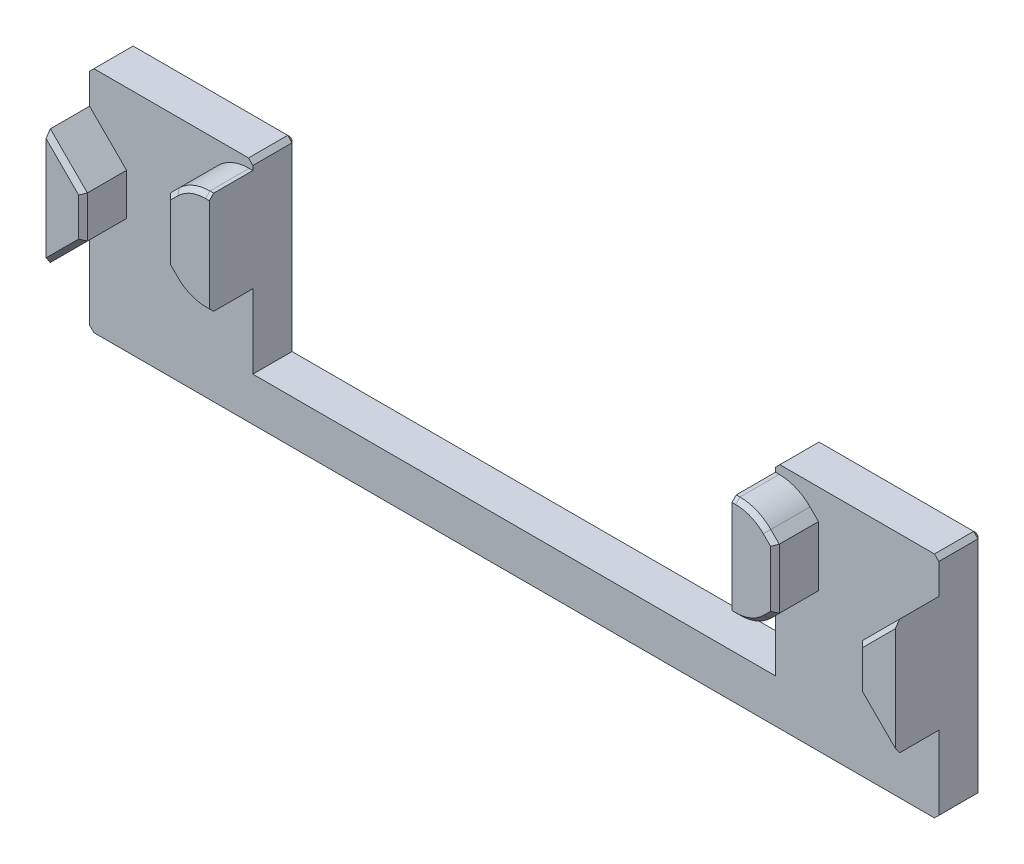
SolidWorks part; units mm, degrees
ref_plane "Front" through (0, 0, 0) normal (0, 0, 1) x (1, 0, 0)
ref_plane "Top" through (0, 0, 0) normal (0, 1, 0) x (1, 0, 0)
ref_plane "Right" through (0, 0, 0) normal (1, 0, 0) x (0, 0, -1)
sketch "Sketch1" plane through (0, 0, 0) normal (0, 0, 1) x (1, 0, 0)
  line L0 (-19.3, -5.25) -> (19.3, -5.25)
  line L5 (19.5, -5.05) -> (19.5, 5.05)
  line L6 (19.3, 5.25) -> (12.2, 5.25)
  line L7 (12, 5.05) -> (12, -3.25)
  line L8 (12, -3.25) -> (-12, -3.25)
  line L9 (-12, -3.25) -> (-12, 5.05)
  line L10 (-12.2, 5.25) -> (-19.3, 5.25)
  line L11 (-19.5, 5.05) -> (-19.5, -5.05)
  line L12 (19.5, 5.05) -> (19.5, -5.05) construction
  line L13 (19.3, 5.25) -> (12, 5.25) construction
  line L14 (19.3, -5.25) -> (-19.3, -5.25) construction
  line L15 (19.5, 5.05) -> (19.3, 5.25)
  line L16 (-12, 5.25) -> (-19.3, 5.25) construction
  line L17 (-19.5, 5.05) -> (-19.5, -5.05) construction
  line L18 (12.2, 5.25) -> (12, 5.05)
  line L19 (19.3, -5.25) -> (19.5, -5.05)
  line L20 (-19.5, -5.05) -> (-19.3, -5.25)
  line L21 (-19.3, 5.25) -> (-19.5, 5.05)
  line L22 (-12, 5.05) -> (-12.2, 5.25)
  point P0 (-19.5, -5.25)
  point P1 (19.5, -5.25)
  point P2 (19.5, 5.25)
  point P4 (12, 5.25)
  point P6 (-19.5, 5.25)
  point P13 (-12, 5.25)
  point P32 (19.5, -5.0528)
  point P33 (19.5, 5.062)
  point P34 (11, 5.0634)
  point P35 (-11, 5.05)
  point P36 (-19.5, 5.05)
  point P37 (-19.5, -5.0409)
  dimension "D1" = 45
  dimension "D3" = 45
  dimension "D6" = 0.2
  dimension "D5" = 45
  dimension "D7" = 45
  dimension "D12" = 0.2
  dimension "D8" = 45
  dimension "D11" = 0.2
  dimension "D9" = 0.2
  dimension "D10" = 45
  dimension "D2" = 0.2
  dimension "D4" = 0.2
extrude "Boss-Extrude1" add sketch "Sketch1" against normal blind 2
sketch "Sketch3" plane through (0, 0, 0) normal (0, 0, 1) x (1, 0, 0)
  line L12 (12, 4.85) -> (12, 0.15)
  line L13 (12, 5.05) -> (12, -3.25) construction
  line L20 (13.975, 1.125) -> (13.975, 3.875)
  line L24 (13.975, 3.875) -> (13.5858, 4.2642)
  line L26 (12.1716, 4.85) -> (11.3284, 4.85)
  line L28 (9.9142, 4.2642) -> (9.5, 3.85)
  line L30 (9.5, 3.85) -> (9.5, 1.15)
  line L32 (9.5, 1.15) -> (9.9142, 0.7358)
  line L36 (11.3284, 0.15) -> (12.1716, 0.15)
  line L37 (13.5858, 0.7358) -> (13.975, 1.125)
  line L38 (13.975, 1.125) -> (13.975, 3.875)
  line L39 (13.975, 3.875) -> (13.5858, 4.2642)
  line L40 (12.1716, 4.85) -> (11.3284, 4.85)
  line L41 (9.9142, 4.2642) -> (9.5, 3.85)
  line L42 (9.5, 3.85) -> (9.5, 1.15)
  line L43 (9.5, 1.15) -> (9.9142, 0.7358)
  line L44 (11.3284, 0.15) -> (12.1716, 0.15)
  line L45 (13.5858, 0.7358) -> (13.975, 1.125)
  arc A10 (13.5858, 4.2642) -> (12.1716, 4.85) centre (12.1716, 2.85) ccw
  arc A11 (11.3284, 4.85) -> (9.9142, 4.2642) centre (11.3284, 2.85) ccw
  arc A12 (9.9142, 0.7358) -> (11.3284, 0.15) centre (11.3284, 2.15) ccw
  arc A13 (12.1716, 0.15) -> (13.5858, 0.7358) centre (12.1716, 2.15) ccw
  arc A14 (13.5858, 4.2642) -> (12.1716, 4.85) centre (12.1716, 2.85) ccw
  arc A15 (11.3284, 4.85) -> (9.9142, 4.2642) centre (11.3284, 2.85) ccw
  arc A16 (9.9142, 0.7358) -> (11.3284, 0.15) centre (11.3284, 2.15) ccw
  arc A17 (12.1716, 0.15) -> (13.5858, 0.7358) centre (12.1716, 2.15) ccw
  point P13 (11.5851, 0.15)
  dimension "D1" = 0
extrude "Slot Aligner" add sketch "Sketch3" along normal blind 2 contours L44 A17 L45 L38 L39 A14 L40 A15 L12 A16 region at (12.9111, 2.5, 0)
mirror "Mirror3" about plane through (0, 0, 0) normal (1, 0, 0) of "Slot Aligner"
sketch "Sketch4" plane through (0, 0, 0) normal (0, 0, 1) x (1, 0, 0)
  line L4 (19.4, 3.5586) -> (19.5, 3.6586)
  line L5 (19.5, 3.8) -> (19.5, -1.8) construction
  line L6 (19.5, 3.6586) -> (19.5, -1.6586)
  line L7 (19.5, -1.6586) -> (19.4, -1.5586)
  line L8 (19.4, -1.5586) -> (19.4, 3.5586)
  line L9 (19.4, 3.5586) -> (17.8, 1.9586)
  line L10 (17.8, 1.9586) -> (17.8, 0.0414)
  line L11 (17.8, 0.0414) -> (19.4, -1.5586)
  line L12 (19.4, -1.5586) -> (19.4, 3.5586) construction
  line L13 (19.4, 3.5586) -> (17.8, 1.9586)
  line L14 (17.8, 1.9586) -> (17.8, 0.0414)
  line L15 (17.8, 0.0414) -> (19.4, -1.5586)
  point P5 (19.3245, 3.483)
  point P8 (19.4302, -1.5888)
  point P9 (19.5, -1.623)
  point P10 (19.3527, 3.5113)
  point P12 (19.2978, 3.4563)
  point P14 (19.4549, -1.6135)
  dimension "D1" = 0.1
extrude "Aligner" add sketch "Sketch4" along normal blind 2
mirror "Aligners" about plane through (0, 0, 0) normal (1, 0, 0) of "Aligner"
chamfer "Deburs" distance 0.2 angle 45 34 edges at (12, 0.9, -2) (12.1, 5.15, -2) (15.75, 5.25, -2) (19.4, 5.15, -2) (19.5, 0, -2) (19.4, -5.15, -2) (0, -5.25, -2) (-19.4, -5.15, -2) (-19.5, 0, -2) (-19.4, 5.15, -2) (-15.75, 5.25, -2) (-12.1, 5.15, -2) (-12, 0.9, -2) (0, -3.25, -2) (-18.65, 2.8086, 2) (-18.65, -0.8086, 2) (-17.8, 1, 2) (18.65, -0.8086, 2) (17.8, 1, 2) (18.65, 2.8086, 2) (-12.0858, 4.85, 2) (-12.0858, 0.15, 2) (-12.9369, 4.6978, 2) (-12.9369, 0.3022, 2) (-13.7804, 4.0696, 2) (-13.7804, 0.9304, 2) (-13.975, 2.5, 2) (12.0858, 4.85, 2) (12.0858, 0.15, 2) (12.9369, 4.6978, 2) (12.9369, 0.3022, 2) (13.7804, 4.0696, 2) (13.975, 2.5, 2) (13.7804, 0.9304, 2)
